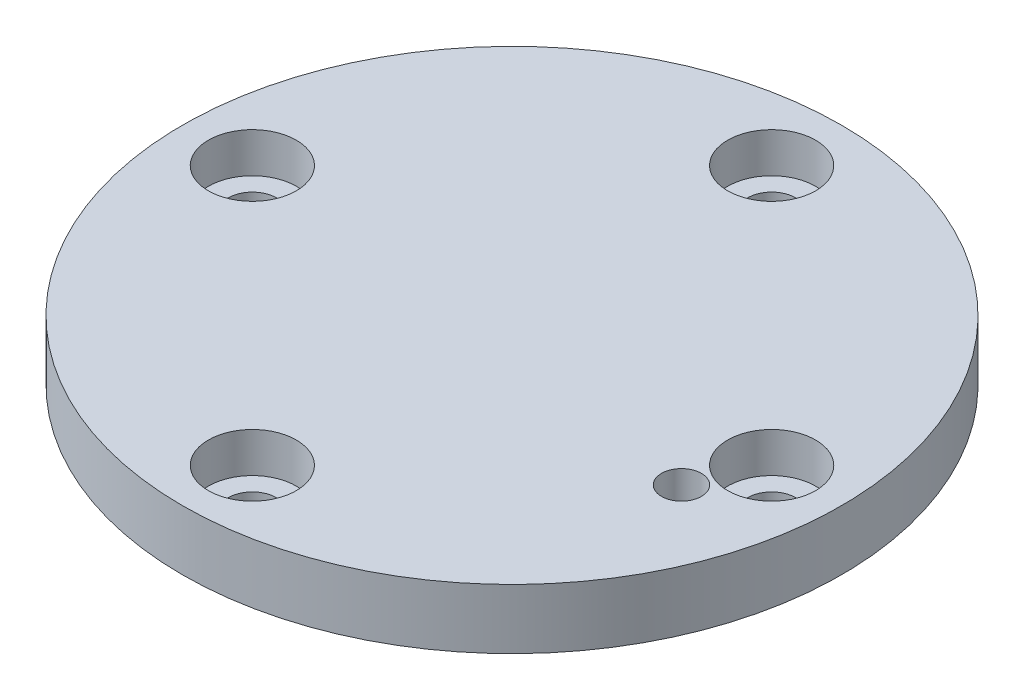
SolidWorks part; units mm, degrees
material "6061-T6 (SS)"
ref_plane "Front Plane" through (0, 0, 0) normal (0, 0, 1) x (1, 0, 0)
ref_plane "Top Plane" through (0, 0, 0) normal (0, 1, 0) x (1, 0, 0)
ref_plane "Right Plane" through (0, 0, 0) normal (1, 0, 0) x (0, 0, -1)
sketch "Sketch1" plane through (0, 0, 0) normal (0, 1, 0) x (1, 0, 0)
  circle A0 centre (0, 0) radius 16.5
  dimension "D1" = 33
extrude "Boss-Extrude1" add sketch "Sketch1" along normal blind 3
sketch "Sketch3" plane through (0, 3, 0) normal (0, 1, 0) x (1, 0, 0)
  circle A0 centre (0, -10.25) radius 0.25
  circle A1 centre (0, 0) radius 9.8
  dimension "D1" = 0.5
  dimension "D2" = 10.25
  dimension "D3" = 19.6
sketch "Sketch4" plane through (0, 3, 0) normal (0, -1, 0) x (1, 0, 0)
  line L0 (0, 0) -> (13.2597, 13.2597) construction
  circle A0 centre (7.7782, 7.7782) radius 1
  dimension "D2" = 2
  dimension "D1" = 11
sketch "Sketch5" plane through (0, 3, 0) normal (0, 1, 0) x (1, 0, 0)
  circle A0 centre (0, 0) radius 11
  dimension "D1" = 22
hole_wizard "CBORE for M2 SHCS1" positions "Sketch6" profile "Sketch7" counterbore size "M2" standard "ANSI Metric" end condition through all
sketch "Sketch6" plane through (0, 3, 0) normal (0, 1, 0) x (1, 0, 0)
  point P0 (13, 0)
  dimension "D1" = 13
sketch "Sketch7" plane through (13, 3, 0) normal (1, 0, 0) x (0, 0, 1)
  line L0 (0, 0) -> (0, 3)
  line L1 (0, 3) -> (1.2, 3)
  line L3 (1.2, 3) -> (1.2, 2)
  line L4 (1.2, 2) -> (2.2, 2)
  line L5 (2.2, 2) -> (2.2, 0)
  line L7 (2.2, 0) -> (0, 0)
  line L11 (0, -6.35) -> (0, 107.95) construction
  dimension "Thru Hole Dia." = 2.4
  dimension "Thru Hole Depth" = 3
  dimension "C'Bore Dia." = 4.4
  dimension "C'Bore Depth" = 2
pattern_circular "CirPattern1" count 4 over 360 about axis through (0, 3, 0) along (0, 1, 0) of "CBORE for M2 SHCS1"
sketch "Sketch8" plane through (0, 0, 0) normal (0, -1, 0) x (1, 0, 0)
  circle A0 centre (6, 0) radius 0.5
  dimension "D1" = 1
  dimension "D2" = 6
extrude "Cut-Extrude1" cut sketch "Sketch8" against normal blind 1.5
sketch "Sketch9" plane through (0, 3, 0) normal (0, 1, 0) x (1, 0, 0)
  line L0 (13, 0) -> (0, 0) construction
  line L1 (0, 0) -> (11.5911, -3.1058) construction
  circle A0 centre (11.5911, -3.1058) radius 1
  dimension "D1" = 2
  dimension "D2" = 12
  dimension "D3" = 15
extrude "Cut-Extrude2" cut sketch "Sketch9" against normal blind 10
